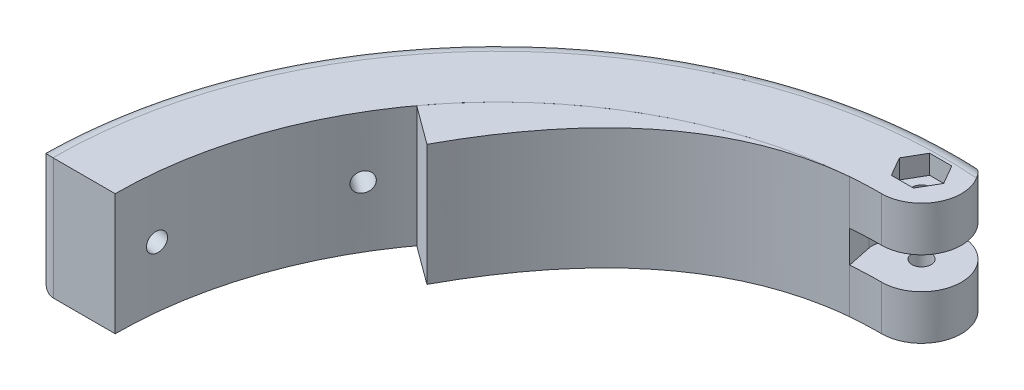
SolidWorks part; units mm, degrees
ref_plane "Front Plane" through (0, 0, 0) normal (0, 0, 1) x (1, 0, 0)
ref_plane "Top Plane" through (0, 0, 0) normal (0, 1, 0) x (1, 0, 0)
ref_plane "Right Plane" through (0, 0, 0) normal (1, 0, 0) x (0, 0, -1)
sketch "Sketch1" plane through (0, 0, 0) normal (0, 1, 0) x (1, 0, 0)
  line L0 (-0.2546, -0.0735) -> (24.7454, -0.0735)
  line L2 (144.7454, 119.9265) -> (144.7454, 144.9265)
  line L4 (144.7454, -153.9705) -> (144.7454, 153.8235) construction
  arc A0 (24.7454, -0.0735) -> (144.7454, 119.9265) centre (144.7454, -0.0735) cw
  arc A1 (-0.2546, -0.0735) -> (144.7454, 144.9265) centre (144.7454, -0.0735) cw
  point P7 (144.7454, -0.0735)
  point P11 (144.7454, -0.0735)
  dimension "D1" = 25
extrude "Boss-Extrude1" add sketch "Sketch1" along normal blind 38
extrude "Cut-Extrude1" cut sketch "Sketch2" against normal through all
sketch "Sketch2" plane through (187.0795, -46.1724, -236.427) normal (0.8056, 0, 0.5924) x (0.5924, 0.0036, -0.8056)
  circle A0 centre (-227.475, 65.9963) radius 3
extrude "Cut-Extrude2" cut sketch "Sketch3" against normal through all
sketch "Sketch3" plane through (59.9415, -46.1724, -112.2008) normal (0.9788, 0, 0.2048) x (0.2045, 0.0528, -0.9774)
  circle A0 centre (-101.2299, 70.6123) radius 3
sketch "Sketch4" plane through (0, 38, 0) normal (0, 1, 0) x (1, 0, 0)
  line L0 (144.7454, 119.9265) -> (144.7454, 144.9265) construction
  line L1 (144.7454, 144.9265) -> (144.7454, -18.1646) construction
  line L2 (0, 0) -> (179.8224, 0) construction
  line L4 (144.7454, 141.9265) -> (144.7454, 144.9265)
  line L5 (135.2454, 132.4265) -> (132.5495, 131.7962)
  line L6 (132.5495, 131.7962) -> (135.1075, 119.5386)
  arc A0 (144.7454, 119.9265) -> (144.7454, 144.9265) centre (144.7454, 132.4265) ccw
  circle A2 centre (144.7454, 132.4265) radius 3
  arc A3 (144.7454, 119.9265) -> (135.1075, 119.5386) centre (144.7454, 0) ccw
  arc A4 (144.7454, 144.9265) -> (144.7454, 119.9265) centre (144.7454, 132.4265) ccw construction
  arc A6 (144.7454, 141.9265) -> (135.2454, 132.4265) centre (144.7454, 132.4265) ccw
  point P16 (132.5495, 131.7962)
  dimension "D1" = 9.5
  dimension "D2" = 6
extrude "Boss-Extrude2" add sketch "Sketch4" against normal up to surface (38 mm away) up to face at (64.7746, 0, -79.8973)
extrude "Cut-Extrude3" cut sketch "Sketch4<2>" against normal blind 24
sketch "Sketch4<2>" plane through (0, 38, 0) normal (0, 1, 0) x (1, 0, 0) same geometry as "Sketch4"
extrude "Boss-Extrude3" add sketch "Sketch4<3>" against normal blind 14
sketch "Sketch4<3>" plane through (0, 38, 0) normal (0, 1, 0) x (1, 0, 0) same geometry as "Sketch4"
extrude "Cut-Extrude4" cut sketch "Sketch4<4>" against normal through all contours A2
sketch "Sketch4<4>" plane through (0, 38, 0) normal (0, 1, 0) x (1, 0, 0) same geometry as "Sketch4"
fillet "Fillet1" radius 5.5 2 edges at (42.2149, 0, -102.457) (42.2149, 38, -102.457) tangent propagation no
fillet "Fillet2" radius 5.5 2 edges at (144.7454, 19, -141.9265) (132.5495, 19, -131.7962)
fillet "Fillet3" radius 5.5 1 edges at (-0.2546, 19, 0.0735) tangent propagation no
sketch "Sketch5" plane through (0, 38, 0) normal (0, 1, 0) x (1, 0, 0)
  line L1 (151.6736, 132.4265) -> (148.2095, 138.4265)
  line L2 (148.2095, 138.4265) -> (141.2813, 138.4265)
  line L3 (141.2813, 138.4265) -> (137.8172, 132.4265)
  line L4 (137.8172, 132.4265) -> (141.2813, 126.4265)
  line L5 (141.2813, 126.4265) -> (148.2095, 126.4265)
  line L6 (148.2095, 126.4265) -> (151.6736, 132.4265)
  circle A0 centre (144.7454, 132.4265) radius 6 construction
  dimension "D1" = 12
extrude "Cut-Extrude5" cut sketch "Sketch5" against normal blind 6
sketch "Sketch6" plane through (0, 38, 0) normal (0, 1, 0) x (1, 0, 0)
  line L0 (5.2454, -0.0724) -> (24.7454, -0.0735) construction
  line L1 (24.7454, -0.0735) -> (213.2224, -0.0735) construction
  line L2 (60.1576, 62.1307) -> (48.0733, 71.0172)
  line L3 (56.5559, 81.3021) -> (56.5553, 81.3052)
  arc A0 (135.1074, 119.5388) -> (24.7454, -0.0735) centre (144.7454, -0.0735) ccw construction
  arc A1 (48.0733, 71.0172) -> (135.1074, 119.5388) centre (144.7525, -0.0801) cw
  spline S0 degree 2 poles (60.1576, 62.1307) (88.8391, 115.1567) (135.1074, 119.5388) knots 0 0 0 0.907301 0.907301 0.907301
  dimension "D1" = 36.33
  dimension "D3" = 43.03
  dimension "D4" = 19.51
extrude "Boss-Extrude4" add sketch "Sketch6" against normal up to surface (38 mm away) separate body contours L2 S0 A1 region at (72.5735, 38, -87.2183) up to face at (144.7454, 0, -135.4265)
